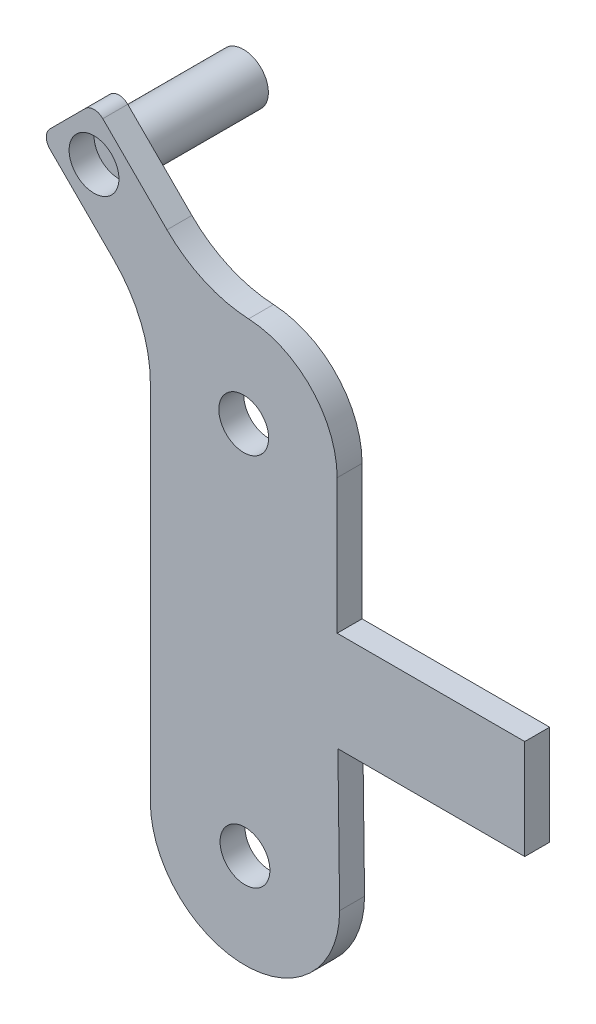
SolidWorks part; units mm, degrees
ref_plane "Front Plane" through (0, 0, 0) normal (0, 0, 1) x (1, 0, 0)
ref_plane "Top Plane" through (0, 0, 0) normal (0, 1, 0) x (1, 0, 0)
ref_plane "Right Plane" through (0, 0, 0) normal (1, 0, 0) x (0, 0, -1)
sketch "Sketch1" plane through (0, 0, 0) normal (0, 0, 1) x (1, 0, 0)
  line L0 (2.0694, -2.4078) -> (2.208, -13.596)
  line L1 (-12.992, 15.5192) -> (-12.992, -13.596)
  line L3 (-16.8058, 31.9603) -> (-11.6547, 26.8093)
  line L4 (2.008, 16.404) -> (2.008, 5.5922)
  line L5 (2.008, 5.5922) -> (17.0694, 5.5922)
  line L6 (-18.22, 31.9603) -> (-21.0484, 29.1319)
  line L7 (2.0694, -2.4078) -> (17.0694, -2.4078)
  line L8 (17.0694, 5.5922) -> (17.0694, -2.4078)
  line L10 (-21.0484, 27.7177) -> (-15.921, 22.5903)
  arc A0 (2.008, 16.404) -> (-5.1027, 23.8939) centre (-5.492, 16.404) ccw
  circle A1 centre (-5.492, 16.404) radius 2
  circle A2 centre (-5.392, -13.596) radius 2
  arc A3 (-12.992, -13.596) -> (2.2056, -13.4078) centre (-5.392, -13.596) ccw
  arc A4 (-5.1027, 23.8939) -> (-11.6547, 26.8093) centre (-4.5837, 33.8804) cw
  arc A5 (-12.992, 15.5192) -> (-15.921, 22.5903) centre (-22.992, 15.5192) ccw
  circle A6 centre (-17.5129, 28.4248) radius 2
  arc A7 (-21.0484, 29.1319) -> (-21.0484, 27.7177) centre (-20.3413, 28.4248) ccw
  arc A8 (-16.8058, 31.9603) -> (-18.22, 31.9603) centre (-17.5129, 31.2532) ccw
  point P10 (2.008, 16.404)
  point P16 (-12.5631, 23.475)
  point P29 (-21.7555, 28.4248)
  point P32 (-17.5129, 32.6674)
  dimension "D1" = 15
  dimension "D6" = 4
  dimension "D7" = 4
  dimension "D8" = 4
  dimension "D2" = 11
  dimension "D3" = 10
  dimension "D11" = 10
  dimension "D12" = 1
  dimension "D13" = 1
  dimension "D4" = 8
  dimension "D5" = 15
  dimension "D9" = 135
  dimension "D10" = 6
  dimension "D14" = 17
extrude "Boss-Extrude1" add sketch "Sketch1" along normal blind 2 contours L1 A3 L0 L7 L8 L5 L4 A0 A1 A2 region at (-3.9541, 3.4148, 0)
sketch "Sketch2" plane through (0, 0, 0) normal (0, 0, -1) x (-1, 0, 0)
  circle A0 centre (17.5129, 28.4248) radius 2
extrude "Boss-Extrude2" add sketch "Sketch2" along normal blind 10 separate body
